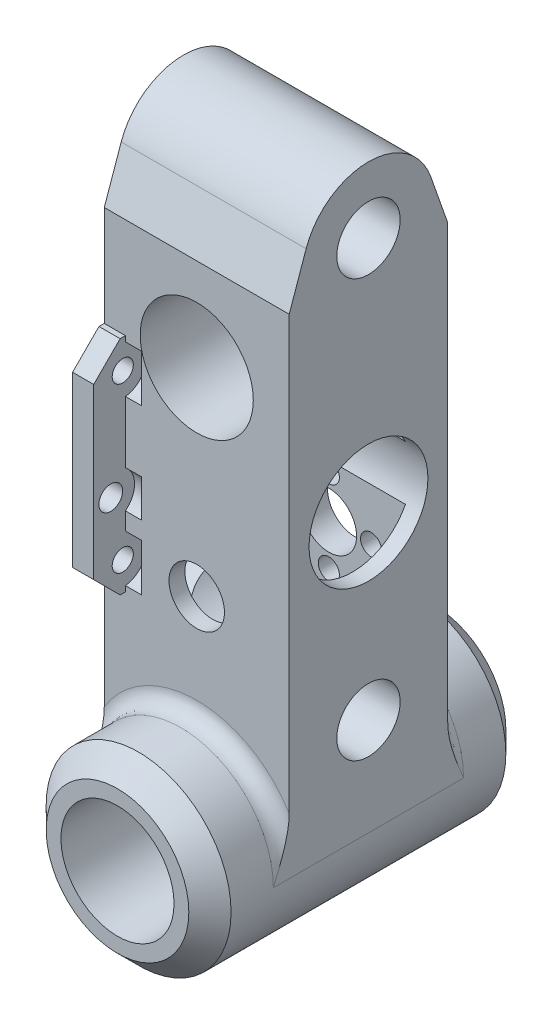
SolidWorks part; units mm, degrees
note: The reader was unsure of these and kept them because the rebuilt part matched: shared geometry of "Sketch1<3>", "Sketch1<4>", "Sketch3<2>", "Sketch1<6>", "Sketch1<7>", "Sketch5<3>", "Sketch1<8>", "Sketch7<2>", "Sketch1<9>", "Sketch3<3>".
material "ABS"
ref_plane "Front Plane" through (0, 0, 0) normal (0, 0, 1) x (1, 0, 0)
ref_plane "Top Plane" through (0, 0, 0) normal (0, 1, 0) x (1, 0, 0)
ref_plane "Right Plane" through (0, 0, 0) normal (1, 0, 0) x (0, 0, -1)
sketch "Sketch1" plane through (0, 0, 0) normal (0, 0, 1) x (1, 0, 0)
  line L0 (0, 16.25) -> (-10.8354, 16.25) construction
  line L1 (0, 0) -> (24.2411, 0) construction
  line L2 (17.5, 37.5) -> (17.5, -37.5)
  line L3 (0, 20) -> (0, 12.5) construction
  line L4 (-17.5, 37.5) -> (-17.5, -37.5)
  line L5 (14.5, 27.702) -> (14.5, -27.702)
  line L6 (14.5, 37.5) -> (14.5, -37.5) construction
  line L7 (-14.5, 27.702) -> (-14.5, -27.702)
  circle A0 centre (0, 37.5) radius 10.7
  circle A1 centre (0, 37.5) radius 17.5
  circle A2 centre (0, -37.5) radius 17.5
  circle A3 centre (0, -37.5) radius 10.7
  circle A4 centre (0, 0) radius 5.25
  circle A5 centre (0, 0) radius 12.5
  circle A6 centre (8, 0) radius 2
  circle A7 centre (0, -8) radius 2
  circle A8 centre (-8, 0) radius 2
  circle A9 centre (0, 8) radius 2
  point P17 (-12.5, 0)
  point P31 (0, 0)
  dimension "D1" = 21.4
  dimension "D2" = 35
  dimension "D4" = 10.5
  dimension "D5" = 25
  dimension "D6" = 4
  dimension "D3" = 75
  dimension "D7" = 8
  dimension "D9" = 3
  dimension "D8" = 4
extrude "Boss-Extrude1" add sketch "Sketch1" along normal mid plane 30 contours A1 A0 | A2 A3
extrude "Boss-Extrude2" add sketch "Sketch1<3>" along normal mid plane 5
sketch "Sketch1<3>" plane through (0, 0, 0) normal (0, 0, 1) x (1, 0, 0) same geometry as "Sketch1"
extrude "Boss-Extrude3" add sketch "Sketch1<4>" along normal mid plane 30 contours L5 A2 L2 A1 | L4 A2 L7 A1
sketch "Sketch1<4>" plane through (0, 0, 0) normal (0, 0, 1) x (1, 0, 0) same geometry as "Sketch1"
sketch "Sketch3" plane through (0, 0, 0) normal (1, 0, 0) x (0, 0, -1)
  line L0 (0, 20.5) -> (27.0405, 20.5) construction
  line L1 (0, 20.5) -> (0, 60) construction
  circle A0 centre (0, 60) radius 6
  circle A1 centre (0, 60) radius 12.5
  circle A2 centre (0, -19) radius 6
  circle A3 centre (0, -19) radius 12.5
  dimension "D1" = 12
  dimension "D2" = 25
  dimension "D3" = 60
  dimension "D4" = 19
extrude "Boss-Extrude4" add sketch "Sketch3" along normal mid plane 35
extrude "Cut-Extrude1" cut sketch "Sketch3<2>" against normal mid plane 40 contours A2 | A0
sketch "Sketch3<2>" plane through (0, 0, 0) normal (1, 0, 0) x (0, 0, -1) same geometry as "Sketch3"
extrude "Cut-Extrude2" cut sketch "Sketch1<6>" against normal through all both and the other way through all contours A0 | A3
sketch "Sketch1<6>" plane through (0, 0, 0) normal (0, 0, 1) x (1, 0, 0) same geometry as "Sketch1"
sketch "Sketch4" plane through (0, 0, 2.5) normal (0, 0, 1) x (1, 0, 0)
  circle A0 centre (0, 0) radius 12.5
  dimension "D1" = 25
extrude "Cut-Extrude3" cut sketch "Sketch4" along normal through all
extrude "Cut-Extrude4" cut sketch "Sketch1<7>" against normal through all both and the other way through all contours A7
sketch "Sketch1<7>" plane through (0, 0, 0) normal (0, 0, 1) x (1, 0, 0) same geometry as "Sketch1"
mirror "Mirror1" about plane through (0, 0, 0) normal (0, 0, 1) of "Cut-Extrude3"
sketch "Sketch5" plane through (0, 0, -15) normal (0, 0, -1) x (-1, 0, 0)
  line L0 (14.5, 27.702) -> (14.5, -27.702) construction
  line L1 (-14.5, 27.702) -> (-14.5, -27.702) construction
  line L2 (14.5, 27.702) -> (14.5, -27.702)
  line L3 (-14.5, 27.702) -> (-14.5, -27.702)
  line L4 (14.5, -6.7526) -> (10.5192, -6.7526) construction
  line L5 (14.5, -6.7526) -> (-14.5, -6.7526)
  arc A0 (-14.5, 27.702) -> (14.5, 27.702) centre (0, 37.5) ccw construction
  arc A1 (14.5, -27.702) -> (-14.5, -27.702) centre (0, -37.5) ccw construction
  arc A2 (-14.5, 27.702) -> (14.5, 27.702) centre (0, 37.5) ccw
  arc A3 (14.5, -27.702) -> (-14.5, -27.702) centre (0, -37.5) ccw
  circle A4 centre (0, 8) radius 2 construction
  circle A5 centre (0, 8) radius 2
  circle A6 centre (0, 0) radius 5.25 construction
  circle A7 centre (0, 0) radius 5.25
  circle A8 centre (8, 0) radius 2 construction
  circle A9 centre (8, 0) radius 2
  circle A10 centre (-8, 0) radius 2 construction
  circle A11 centre (-8, 0) radius 2
  circle A12 centre (0, -8) radius 2 construction
  circle A13 centre (0, -8) radius 2
  arc A14 (-10.5192, -6.7526) -> (10.5192, -6.7526) centre (0, 0) ccw construction
  arc A15 (-10.5192, -6.7526) -> (10.5192, -6.7526) centre (0, 0) ccw
  line M8 (14.5, 27.702) -> (14.5, -27.702)
  arc M9 (14.5, -27.702) -> (-14.5, -27.702) centre (0, -37.5) ccw
  line M10 (-14.5, -27.702) -> (-14.5, 27.702)
  arc M11 (-14.5, 27.702) -> (14.5, 27.702) centre (0, 37.5) ccw
extrude "Cut-Extrude5" cut sketch "Sketch5" against normal through all contours L5 L3 A11 A9 A7 A5 M8 M11 | L5 A15 A13
extrude "Boss-Extrude5" add sketch "Sketch5<3>" against normal blind 5 contours A13 L5 L3 A11 A9 A7 A5 M8 M11 | A15 L5 L2 M10 M9 | L5 A15 A13
sketch "Sketch5<3>" plane through (0, 0, -15) normal (0, 0, -1) x (-1, 0, 0) same geometry as "Sketch5"
sketch "Sketch6" plane through (0, 0, 0) normal (1, 0, 0) x (0, 0, -1)
  line L0 (15, 55) -> (11.7956, 64.1368)
  line L1 (0, 60) -> (0, 37.5) construction
  line L2 (-15, 37.5) -> (15, 37.5) construction
  line L3 (15, 55) -> (15, 37.5)
  line L4 (15, 26.8) -> (15, 48.2) construction
  line L5 (15, 37.5) -> (-15, 37.5)
  line L6 (-15, 55) -> (-11.7956, 64.1368)
  line L7 (-15, 55) -> (-15, 37.5)
  circle A0 centre (0, 60) radius 12.5 construction
  circle A1 centre (0, 60) radius 12.5
extrude "Boss-Extrude6" add sketch "Sketch6" along normal mid plane 35 contours A1 L1 L5 L3 L0 | L1 A1 L6 L7 L5
extrude "Cut-Extrude6" cut sketch "Sketch1<8>" against normal through all both and the other way through all contours A0
sketch "Sketch1<8>" plane through (0, 0, 0) normal (0, 0, 1) x (1, 0, 0) same geometry as "Sketch1"
sketch "Sketch7" plane through (-17.5, 0, 0) normal (-1, 0, 0) x (0, 0, 1)
  line L0 (0, 15) -> (0, 36) construction
  line L1 (-21, 36) -> (21, 36)
  line L2 (-21, 36) -> (-21, -6)
  line L3 (-21, -6) -> (21, -6)
  line L4 (21, 36) -> (21, -6)
  line L5 (-21, 36) -> (21, -6) construction
  line L6 (-21, -6) -> (21, 36) construction
  line L7 (0, 15) -> (21, 15) construction
  line L8 (0, 0) -> (0, 15) construction
  circle A0 centre (15.5, 30.5) radius 2
  circle A1 centre (-15.5, 30.5) radius 2
  circle A2 centre (-15.5, -0.5) radius 2
  circle A3 centre (15.5, -0.5) radius 2
  circle A4 centre (0, 15) radius 11.25
  point P0 (0, 15)
  line M10 (-15, 55) -> (-15, -37.5)
  dimension "D2" = 4
  dimension "D3" = 31
  dimension "D4" = 22.5
  dimension "D1" = 42
  dimension "D5" = 15
extrude "Boss-Extrude7" add sketch "Sketch7" against normal blind 4
sketch "Sketch8" plane through (-17.5, 0, 0) normal (-1, 0, 0) x (0, 0, 1)
  circle A0 centre (0, 15) radius 11.25
  dimension "D1" = 22.5
extrude "Cut-Extrude7" cut sketch "Sketch8" against normal blind 40
extrude "Cut-Extrude8" cut sketch "Sketch7<2>" against normal blind 4 contours A1 M10 | A1 M10 | A0 | A3 | A2 | A4
sketch "Sketch7<2>" plane through (-17.5, 0, 0) normal (-1, 0, 0) x (0, 0, 1) same geometry as "Sketch7"
sketch "Sketch10" plane through (-13.5, 0, 0) normal (1, 0, 0) x (0, 0, -1)
  circle A0 centre (-15.5, 30.5) radius 4.5
  circle A1 centre (15.5, 30.5) radius 4.5
  circle A2 centre (15.5, -0.5) radius 4.5
  circle A3 centre (-15.5, -0.5) radius 4.5
  point P12 (0, 15)
  dimension "D1" = 9
  dimension "D2" = 4
extrude "Cut-Extrude9" cut sketch "Sketch10" along normal blind 3
sketch "Sketch11" plane through (-17.5, 0, 0) normal (-1, 0, 0) x (0, 0, 1)
  line L0 (-17.7667, 19.1722) -> (0, 15) construction
  line L1 (0, 15) -> (1.9472, 23.2919) construction
  circle A0 centre (0, 15) radius 18.25 construction
  circle A1 centre (-17.7667, 19.1722) radius 2.25
  circle A2 centre (17.7667, 10.8278) radius 2.25
  dimension "D1" = 36.5
  dimension "D2" = 4.5
extrude "Cut-Extrude10" cut sketch "Sketch11" against normal blind 5
sketch "Sketch12" plane through (-13.5, 0, 0) normal (1, 0, 0) x (0, 0, -1)
  circle A0 centre (17.7667, 19.1722) radius 5
  circle A1 centre (-17.7667, 10.8278) radius 5
  dimension "D1" = 10
extrude "Cut-Extrude11" cut sketch "Sketch12" along normal blind 5
chamfer "Chamfer1" distance 5 angle 45 4 edges at (-15.5, -6, -21) (-15.5, -6, 21) (-15.5, 36, 21) (-15.5, 36, -21)
extrude "Boss-Extrude8" add sketch "Sketch1<9>" along normal mid plane 60 contours A2 A3
sketch "Sketch1<9>" plane through (0, 0, 0) normal (0, 0, 1) x (1, 0, 0) same geometry as "Sketch1"
extrude "Cut-Extrude12" cut sketch "Sketch3<3>" against normal mid plane 60 contours A2
sketch "Sketch3<3>" plane through (0, 0, 0) normal (1, 0, 0) x (0, 0, -1) same geometry as "Sketch3"
sketch "Sketch14" plane through (0, 0, 15) normal (0, 0, 1) x (1, 0, 0)
  line L0 (-14.5, -6) -> (14.5, -6)
  line L1 (14.5, 27.702) -> (14.5, -27.702) construction
  line L2 (14.5, -6) -> (14.5, -27.702)
  line L3 (-14.5, -6) -> (-14.5, -27.702)
  arc A0 (14.5, -27.702) -> (-14.5, -27.702) centre (0, -37.5) ccw construction
  arc A1 (14.5, -27.702) -> (-14.5, -27.702) centre (0, -37.5) ccw
extrude "Boss-Extrude9" add sketch "Sketch14" against normal blind 3
sketch "Sketch15" plane through (0, 0, 15) normal (0, 0, 1) x (1, 0, 0)
  line L0 (14.5, 27.702) -> (14.5, -6) construction
  line L1 (14.5, -6) -> (-13.5, -6) construction
  line L2 (14.5, 27.702) -> (14.5, -6)
  line L3 (14.5, -6) -> (-13.5, -6)
  line L4 (-13.5, 20.1539) -> (-13.5, 26.3645) construction
  line L5 (-13.5, -6) -> (-13.5, 26.3645)
  arc A0 (-13.2151, 26.0279) -> (14.5, 27.702) centre (0, 37.5) ccw construction
  arc A1 (-13.5, 26.3645) -> (14.5, 27.702) centre (0, 37.5) ccw
extrude "Boss-Extrude10" add sketch "Sketch15" against normal blind 3
sketch "Sketch16" plane through (-13.5, 0, 0) normal (1, 0, 0) x (0, 0, -1)
  circle A0 centre (-15.5, 30.5) radius 4.5
  circle A1 centre (-15.5, -0.5) radius 4.5
  circle A2 centre (-17.7667, 10.8278) radius 4.5
extrude "Cut-Extrude13" cut sketch "Sketch16" along normal up to surface (3 mm away) up to face at (-10.5, 30.5, 13)
sketch "Sketch17" plane through (0, 0, -15) normal (0, 0, -1) x (-1, 0, 0)
  circle A0 centre (0, 0) radius 5.25 construction
  circle A1 centre (0, 0) radius 5.25
extrude "Cut-Extrude14" cut sketch "Sketch17" against normal through all
chamfer "Chamfer2" distance 4 angle 45 2 edges at (17.5, -37.5, -30) (17.5, -37.5, 30)
fillet "Fillet1" radius 3 2 edges at (0, -20, -15) (0, -20, 15)
